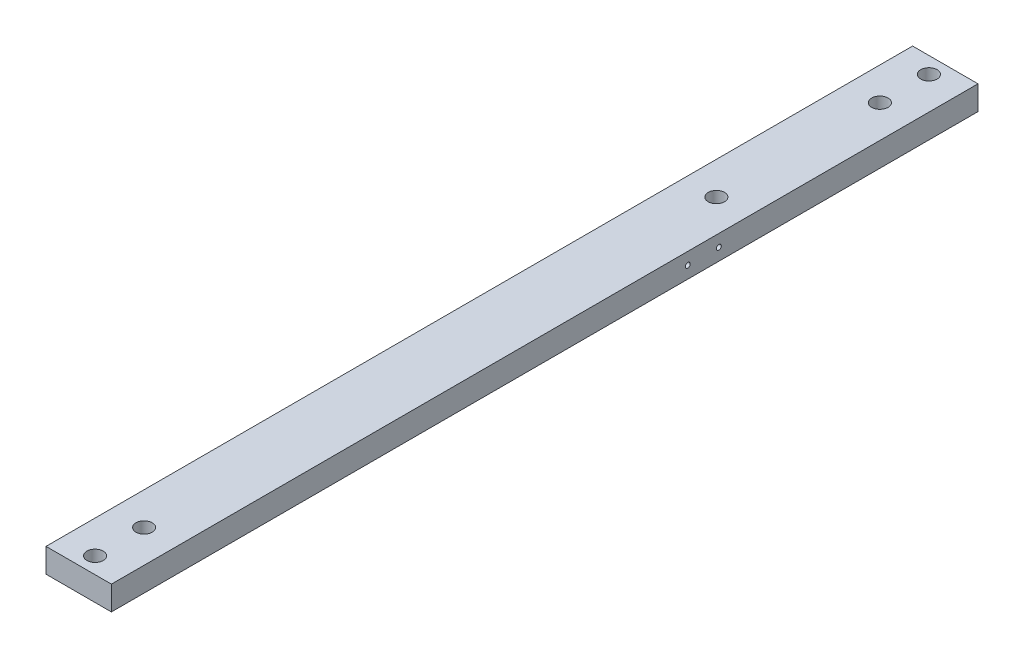
SolidWorks part; units mm, degrees
ref_plane "前视基准面" through (0, 0, 0) normal (0, 0, 1) x (1, 0, 0)
ref_plane "上视基准面" through (0, 0, 0) normal (0, 1, 0) x (1, 0, 0)
ref_plane "右视基准面" through (0, 0, 0) normal (1, 0, 0) x (0, 0, -1)
other "Configuration Table"
sketch "草图1" plane through (0, 0, 0) normal (0, 1, 0) x (1, 0, 0)
  line L1 (0, 0) -> (8, 0)
  line L2 (0, 0) -> (0, -106)
  line L3 (0, -106) -> (8, -106)
  line L4 (8, 0) -> (8, -106)
  dimension "D1" = 106
  dimension "D2" = 8
extrude "凸台-拉伸1" add sketch "草图1" along normal blind 2.95
sketch "草图2" plane through (0, 2.95, 0) normal (0, 1, 0) x (1, 0, 0)
  line L0 (0, -2) -> (8, -2)
  line L1 (0, 0) -> (0, -106) construction
  line L2 (8, -106) -> (8, 0) construction
  line L3 (8, 0) -> (0, 0) construction
  line L4 (0, -106) -> (8, -106) construction
  circle A0 centre (4, -8) radius 0.7
  circle A1 centre (4, -8) radius 1
  circle A2 centre (4, -2) radius 0.7
  circle A3 centre (4, -2) radius 1
  circle A4 centre (4, -104) radius 0.7
  circle A5 centre (4, -104) radius 1
  circle A6 centre (4, -98) radius 0.7
  circle A7 centre (4, -98) radius 1
  circle A8 centre (4, -28) radius 1
  circle A9 centre (4, -28) radius 0.7
  point P16 (0, 0)
  dimension "D1" = 2
  dimension "D2" = 1.4
  dimension "D3" = 2
  dimension "D4" = 1.4
  dimension "D7" = 2
  dimension "D8" = 1.4
  dimension "D9" = 2
  dimension "D10" = 1.4
  dimension "D5" = 2
  dimension "D6" = 6
  dimension "D11" = 2
  dimension "D12" = 6
  dimension "D13" = 20
extrude "切除-拉伸1" cut sketch "草图2" against normal through all contours A2 | A0 | A6 | A4 | A9
extrude "切除-拉伸2" cut sketch "草图2<3>" against normal blind 1.5 contours A1 | A3 | A5 | A7 | A8
sketch "草图2<3>" plane through (0, 2.95, 0) normal (0, 1, 0) x (1, 0, 0) same geometry as "草图2"
sketch "草图3" plane through (8, 0, 0) normal (1, 0, 0) x (0, 0, -1)
  circle A0 centre (-31.7, 1.475) radius 0.3
  circle A1 centre (-35.5, 1.475) radius 0.3
  dimension "D1" = 0.6
extrude "切除-拉伸3" cut sketch "草图3" against normal through all contours A0 | A1
